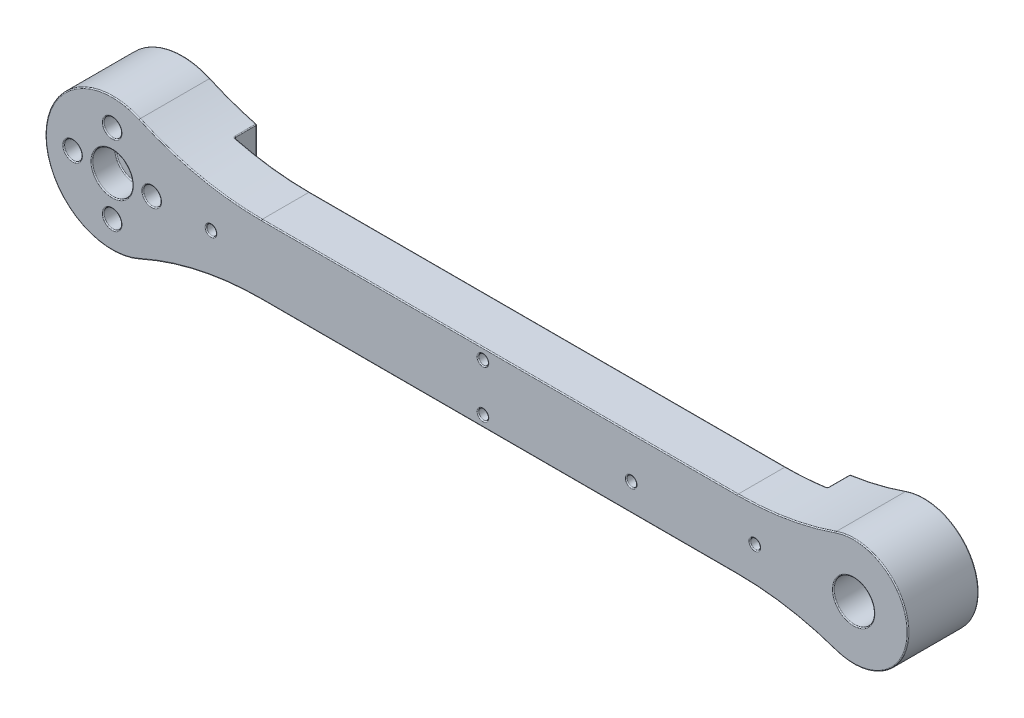
SolidWorks part; units mm, degrees
ref_plane "정면" through (0, 0, 0) normal (0, 0, 1) x (1, 0, 0)
ref_plane "윗면" through (0, 0, 0) normal (0, 1, 0) x (1, 0, 0)
ref_plane "우측면" through (0, 0, 0) normal (1, 0, 0) x (0, 0, -1)
sketch "스케치1" plane through (0, 0, 0) normal (0, 0, 1) x (1, 0, 0)
  line L0 (0, 11) -> (50, 11)
  line L1 (50, 11) -> (50, -11)
  line L2 (50, -11) -> (0, -11)
  line L3 (0, 0) -> (78.6227, 0) construction
  line L4 (8.4853, 7) -> (50, 7)
  line L5 (8.4853, -7) -> (50, -7)
  line L7 (0, -8) -> (0, 0) construction
  arc A0 (0, 11) -> (0, -11) centre (0, 0) ccw
  circle A1 centre (0, 0) radius 4.1
  circle A6 centre (0, 0) radius 11
  circle A7 centre (0, -8) radius 1.8
  circle A8 centre (-8, 0) radius 1.8
  circle A9 centre (0, 8) radius 1.8
  circle A10 centre (8, 0) radius 1.8
  point P15 (0, 0)
  point P26 (0, 0)
  dimension "D1" = 22
  dimension "D2" = 3.6
  dimension "D4" = 8.2
  dimension "D3" = 8
  dimension "D6" = 50
  dimension "D7" = 14
  dimension "D5" = 90
  dimension "D9" = 4
extrude "보스-돌출1" add sketch "스케치1" along normal blind 14.3 contours A6 A0 A10 A9 A8 A7 A1 | A6 L5 L1 L4 region at (4.5578, 9.6684, 0) region at (30.0954, 0, 0)
sketch "스케치3" plane through (0, 0, 0) normal (0, 0, -1) x (-1, 0, 0)
  circle A0 centre (0, 0) radius 4.1
  circle A1 centre (0, 0) radius 2.45
  circle M6 centre (0, 0) radius 4.1
  dimension "D1" = 8.2
  dimension "D2" = 4.9
extrude "보스-돌출2" add sketch "스케치3" against normal blind 9.5 contours A1 M6 region at (3.984, 0, 0)
sketch "스케치4" plane through (0, 0, 0) normal (0, 0, -1) x (-1, 0, 0)
  line L3 (-8.4853, 7) -> (-50, 7)
  line L4 (-50, 7) -> (-50, -7)
  line L5 (-50, -7) -> (-8.4853, -7)
  line L6 (-8.4853, 7) -> (-50, 7)
  line L7 (-50, 7) -> (-50, -7)
  line L8 (-50, -7) -> (-8.4853, -7)
  arc A0 (-3, 8) -> (3, 8) centre (0, 8) ccw
  circle A1 centre (-8, 0) radius 1.8
  circle A2 centre (-8, 0) radius 1.8
  circle A3 centre (0, 8) radius 1.8
  circle A4 centre (0, 8) radius 1.8
  circle A5 centre (8, 0) radius 1.8
  circle A6 centre (8, 0) radius 1.8
  circle A7 centre (0, -8) radius 1.8
  circle A8 centre (0, -8) radius 1.8
  circle A9 centre (0, 0) radius 2.45
  circle A10 centre (0, 0) radius 2.45
  arc A11 (8, 3) -> (8, -3) centre (8, 0) ccw
  circle A12 centre (-8, 0) radius 3
  arc A13 (3, -8) -> (-3, -8) centre (0, -8) ccw
  circle A14 centre (0, 8) radius 3
  circle A15 centre (8, 0) radius 3
  circle A16 centre (0, -8) radius 3
  arc A17 (-8.4853, -7) -> (-8.4853, 7) centre (0, 0) ccw
  circle A18 centre (0, 0) radius 13.5
  circle M9 centre (-8, 0) radius 1.8
  circle M10 centre (0, 8) radius 1.8
  circle M11 centre (8, 0) radius 1.8
  circle M12 centre (0, -8) radius 1.8
  dimension "D6" = 6
  dimension "D8" = 27
  dimension "D1" = 0
  dimension "D2" = 0
  dimension "D3" = 0
  dimension "D4" = 0
  dimension "D5" = 0
  dimension "D7" = 0
sketch "스케치6" plane through (0, 0, 0) normal (0, 0, -1) x (-1, 0, 0)
  line L0 (-50, 7) -> (-50, -7)
  line L1 (-50, -7) -> (-141.5147, -7)
  line L2 (-50, 7) -> (-141.5147, 7)
  circle A0 centre (-150, 0) radius 11
  circle A1 centre (-150, 0) radius 4.8
  circle A2 centre (-150, 0) radius 4.1
  line M22 (-50, 7) -> (-50, -7)
  dimension "D1" = 22
  dimension "D2" = 9.6
  dimension "D3" = 8.2
  dimension "D4" = 150
extrude "보스-돌출3" add sketch "스케치6" against normal up to surface (14.3 mm away) contours A0 L1 L2 M22 | A0 A1 | A1 A2 region at (94.9009, 0, 0) region at (139.9406, 3.6138, 0) region at (154.6642, 0, 0) up to face at (9.8, 0, 14.3)
sketch "스케치7" plane through (0, 0, 0) normal (0, 0, -1) x (-1, 0, 0)
  line L1 (-135, 7) -> (-15, 7)
  line L2 (-135, 7) -> (-135, -7)
  line L3 (-135, -7) -> (-15, -7)
  line L4 (-15, 7) -> (-15, -7)
  line L5 (-135, 7) -> (-15, -7) construction
  line L6 (-135, -7) -> (-15, 7) construction
  line L7 (-125.1, 2.6) -> (-24.9, 2.6)
  line L8 (-125.1, 2.6) -> (-125.1, -2.6)
  line L9 (-125.1, -2.6) -> (-24.9, -2.6)
  line L10 (-24.9, 2.6) -> (-24.9, -2.6)
  line L11 (-125.1, 2.6) -> (-24.9, -2.6) construction
  line L12 (-125.1, -2.6) -> (-24.9, 2.6) construction
  point P0 (-75, 0)
  point P5 (-75, 0)
  dimension "D1" = 75
  dimension "D2" = 14
  dimension "D3" = 120
  dimension "D4" = 100.2
  dimension "D5" = 5.2
extrude "컷-돌출6" cut sketch "스케치7" against normal blind 4.55 contours L2 L3 L4 L1
extrude "컷-돌출7" cut sketch "스케치7<3>" against normal blind 5.2 from surface contours L7 L10 L9 L8 starting at face at (75, 0, 4.55)
sketch "스케치7<3>" plane through (0, 0, 0) normal (0, 0, -1) x (-1, 0, 0) same geometry as "스케치7"
sketch "스케치8" plane through (0, 0, 4.55) normal (0, 0, -1) x (-1, 0, 0)
  line L0 (0, 0) -> (-78.6227, 0) construction
  line L1 (-135, 7) -> (-135, -7) construction
  line L2 (-15, 7) -> (-15, -7) construction
  line L4 (-50, 7) -> (-141.5147, 7) construction
  line L5 (-50, -7) -> (-141.5147, -7) construction
  circle A0 centre (-20, 0) radius 1
  circle A1 centre (-130, 0) radius 1
  circle A2 centre (-75, 4.8) radius 1
  circle A3 centre (-75, -4.8) radius 1
  dimension "D1" = 2
  dimension "D2" = 2
  dimension "D5" = 2
  dimension "D7" = 2
  dimension "D3" = 5
  dimension "D4" = 5
  dimension "D6" = 2.2
  dimension "D8" = 2.2
extrude "컷-돌출8" cut sketch "스케치8" against normal through all
sketch "스케치9" plane through (0, 0, 4.55) normal (0, 0, -1) x (-1, 0, 0)
  line L0 (-110, 7) -> (-110, -7) construction
  line L1 (-50, 7) -> (-141.5147, 7) construction
  line L2 (-50, -7) -> (-141.5147, -7) construction
  circle A0 centre (-105, -1.5) radius 1
  dimension "D1" = 2
  dimension "D2" = 40
  dimension "D3" = 5
  dimension "D4" = 5.5
extrude "컷-돌출9" cut sketch "스케치9" against normal through all
extrude "컷-돌출10" cut sketch "스케치6<4>" against normal blind 1.8 contours A1 A2 region at (154.6642, 0, 0)
sketch "스케치6<4>" plane through (0, 0, 0) normal (0, 0, -1) x (-1, 0, 0) same geometry as "스케치6"
fillet "필렛3" radius 60 2 edges at (141.5147, -7, 7.15) (141.5147, 7, 7.15)
sketch "스케치10" plane through (0, 0, 14.3) normal (0, 0, 1) x (1, 0, 0)
  circle A0 centre (0, 0) radius 13.5
  circle A1 centre (0, 0) radius 11
  dimension "D1" = 27
extrude "보스-돌출4" add sketch "스케치10" against normal up to surface (14.3 mm away) from surface up to face at (9.8, 0, 0) starting at face at (104, -1.5, 14.3)
fillet "필렛4" radius 60 2 edges at (11.5434, -7, 7.15) (11.5434, 7, 7.15)
extrude "컷-돌출11" cut sketch "스케치4" against normal blind 5 from surface contours A0 A14 M10 | A15 A11 M11 | A12 M9 | A13 A16 M12 region at (2.0613, -10.0613, 0) region at (-10.0613, -2.0613, 0) region at (-2.0613, 10.0613, 0) region at (10.9151, 0, 0) starting at face at (5.4777, 0, 0)
fillet "필렛5" radius 0.2 65 edges at (15, 8.9625, 2.275) (15, -8.9625, 2.275) (135, -7.6044, 2.275) (135, 7.6044, 2.275) (145.2, 0, 1.8) (145.9, 0, 1.8) (-4.1, 0, 9.5) (-2.45, 0, 9.5) (9.8, 0, 14.3) (1.8, 8, 14.3) (-6.2, 0, 14.3) (1.8, -8, 14.3) (4.1, 0, 14.3) (154.1, 0, 14.3) (74, -4.8, 14.3) (74, 4.8, 14.3) (129, 0, 14.3) (19, 0, 14.3) (104, -1.5, 14.3) (136.5755, 7.8511, 14.3) (161, 0, 14.3) (136.5755, -7.8511, 14.3) (78.3627, -7, 14.3) (17.6032, -8.3415, 14.3) (-13.5, 0, 14.3) (17.6032, 8.3415, 14.3) (78.3627, 7, 14.3) (-6.2, 0, 5) (-5, 0, 5) (1.8, -8, 5) (3, -8, 5) (1.8, 8, 5) (3, 8, 5) (9.8, 0, 5) (11, 0, 5) (3, 8, 0) (11, 0, 0) (-2.45, 0, 0) (10.2054, 10.4366, 0) (-13.5, 0, 0) (10.2054, -10.4366, 0) (15, 0, 0) (3, -8, 0) (-5, 0, 0) (22.547, 7.4926, 4.55) (15, 0, 4.55) (22.547, -7.4926, 4.55) (78.3627, -7, 4.55) (130.7634, -7.1513, 4.55) (135, 0, 4.55) (130.7634, 7.1513, 4.55) (78.3627, 7, 4.55) (125.1, 0, 4.55) (75, -2.6, 4.55) (24.9, 0, 4.55) (75, 2.6, 4.55) (74, -4.8, 4.55) (74, 4.8, 4.55) (129, 0, 4.55) (19, 0, 4.55) (140.7478, 8.7149, 0) (135, 0, 0) (140.7478, -8.7149, 0) (161, 0, 0) (145.2, 0, 0)
